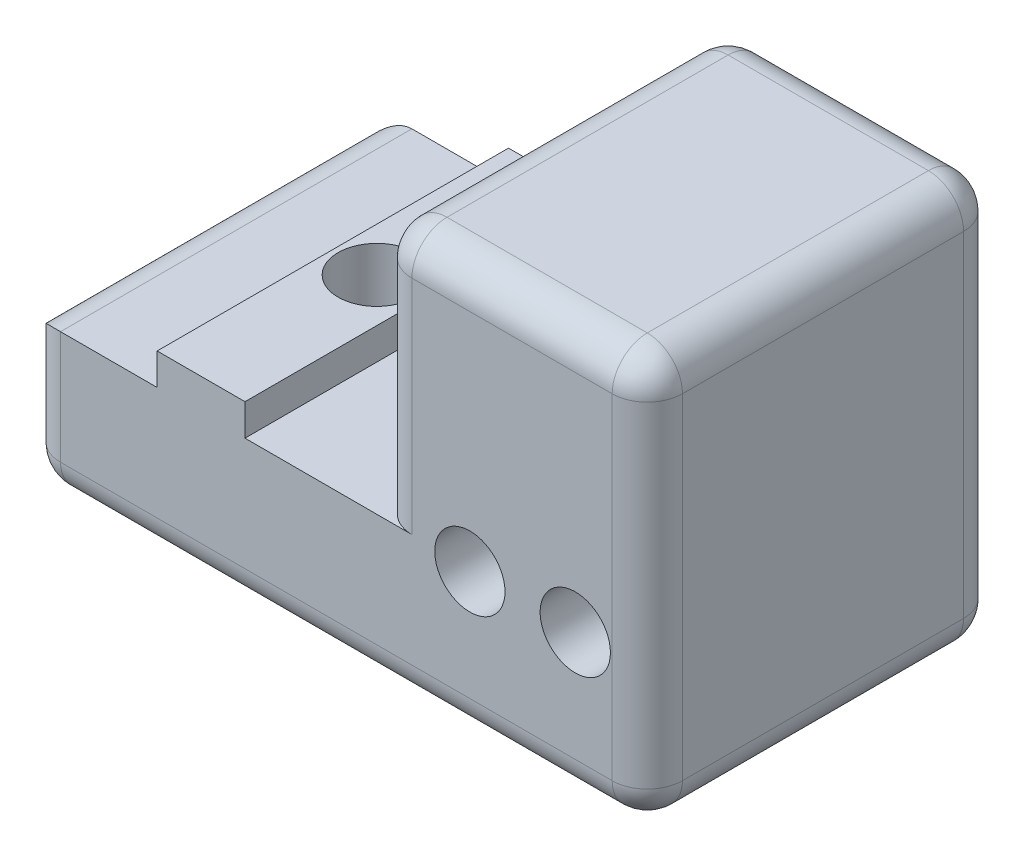
SolidWorks part; units mm, degrees
ref_plane "Front Plane" through (0, 0, 0) normal (0, 0, 1) x (1, 0, 0)
ref_plane "Top Plane" through (0, 0, 0) normal (0, 1, 0) x (1, 0, 0)
ref_plane "Right Plane" through (0, 0, 0) normal (1, 0, 0) x (0, 0, -1)
sketch "Sketch1" plane through (0, 0, 0) normal (0, 0, 1) x (1, 0, 0)
  line L0 (-15.2, -92.5791) -> (-50.6006, -92.5791)
  line L1 (-27.6006, -92.5791) -> (-15, -92.5791) construction
  line L2 (-15.2, -92.5791) -> (-15.2, -69.5033)
  line L3 (-50.6006, -84.1433) -> (-43.1006, -84.1433)
  line L4 (-30.6006, -84.1433) -> (-30.6006, -69.5033)
  line L6 (-30.6006, -69.5033) -> (-15.2, -69.5033)
  line L7 (-50.6006, -84.3933) -> (-50.6006, -79.1433) construction
  line L8 (-50.6006, -92.5791) -> (-50.6006, -84.1433)
  line L9 (-15, -87.5791) -> (-15, -92.5791) construction
  line L10 (-27.5003, -84.3159) -> (-17.1003, -84.3159) construction
  line L11 (-22.3003, -84.3159) -> (-22.3003, -77.3159) construction
  line L12 (-43.4406, -82.3433) -> (-37.7606, -82.3433) construction
  line L14 (-43.1006, -84.1433) -> (-43.1006, -82.3433)
  line L15 (-43.1006, -82.3433) -> (-38.1006, -82.3433)
  line L16 (-38.1006, -84.1433) -> (-38.1006, -82.3433)
  line L17 (-38.1006, -84.1433) -> (-30.6006, -84.1433)
  arc A0 (-25.3003, -82.1159) -> (-25.3003, -86.5159) centre (-25.3003, -84.3159) ccw construction
  arc A1 (-19.3003, -86.5159) -> (-19.3003, -82.1159) centre (-19.3003, -84.3159) ccw construction
  circle A2 centre (-25.3003, -84.3159) radius 2
  circle A3 centre (-19.3003, -84.3159) radius 2
  circle A4 centre (-22.3003, -77.3159) radius 3.05
  point P11 (-40.6006, -82.3433)
  point P41 (-40.6006, -82.3433)
  dimension "D2" = 4
  dimension "D3" = 4
  dimension "D4" = 6.1
  dimension "D1" = 0.2
  dimension "D5" = 7
  dimension "D6" = 5
extrude "Boss-Extrude1" add sketch "Sketch1" along normal blind 20
sketch "Sketch2" plane through (0, -92.5791, 0) normal (0, -1, 0) x (1, 0, 0)
  line L0 (-29.3961, 0) -> (-9.3901, 0) construction
  line L1 (-30.6006, 0) -> (-30.6006, 20) construction
  line L2 (-50.6006, 0) -> (-15.2, 0) construction
  line L3 (-50.6006, 20) -> (-15.2, 20) construction
  line L4 (-50.6006, 20) -> (-50.6006, 0) construction
  line L5 (-30.6006, 0) -> (-50.6006, 20) construction
  circle A0 centre (-40.6006, 10) radius 3.7
  circle A1 centre (-40.6006, 10) radius 2.2
  dimension "D2" = 4.4
  dimension "D3" = 7.4
  dimension "D1" = 20
extrude "Cut-Extrude1" cut sketch "Sketch2" against normal blind 27.508 contours A1 region at (-40.6006, -92.5791, 10)
extrude "Cut-Extrude2" cut sketch "Sketch2<3>" against normal offset from surface (6.4357 mm away) 2 up to face at (-34.3506, -84.1433, 10)
sketch "Sketch2<3>" plane through (0, -92.5791, 0) normal (0, -1, 0) x (1, 0, 0) same geometry as "Sketch2"
extrude "Boss-Extrude2" add sketch "Sketch1<2>" along normal up to surface (20 mm away) from offset 6.3 contours A4 region at (-22.3003, -77.3159, 0) up to face at (-35.5205, -82.5425, 20)
sketch "Sketch1<2>" plane through (0, 0, 0) normal (0, 0, 1) x (1, 0, 0) same geometry as "Sketch1"
fillet "Fillet1" radius 2 15 edges at (-50.6006, -84.1433, 10) (-50.6006, -88.3612, 20) (-50.6006, -88.3612, 0) (-30.6006, -76.8233, 0) (-30.6006, -76.8233, 20) (-30.6006, -69.5033, 10) (-22.9003, -69.5033, 0) (-15.2, -69.5033, 10) (-15.2, -81.0412, 0) (-32.9003, -92.5791, 0) (-32.9003, -92.5791, 20) (-22.9003, -69.5033, 20) (-15.2, -81.0412, 20) (-15.2, -92.5791, 10) (-50.6006, -92.5791, 10)
